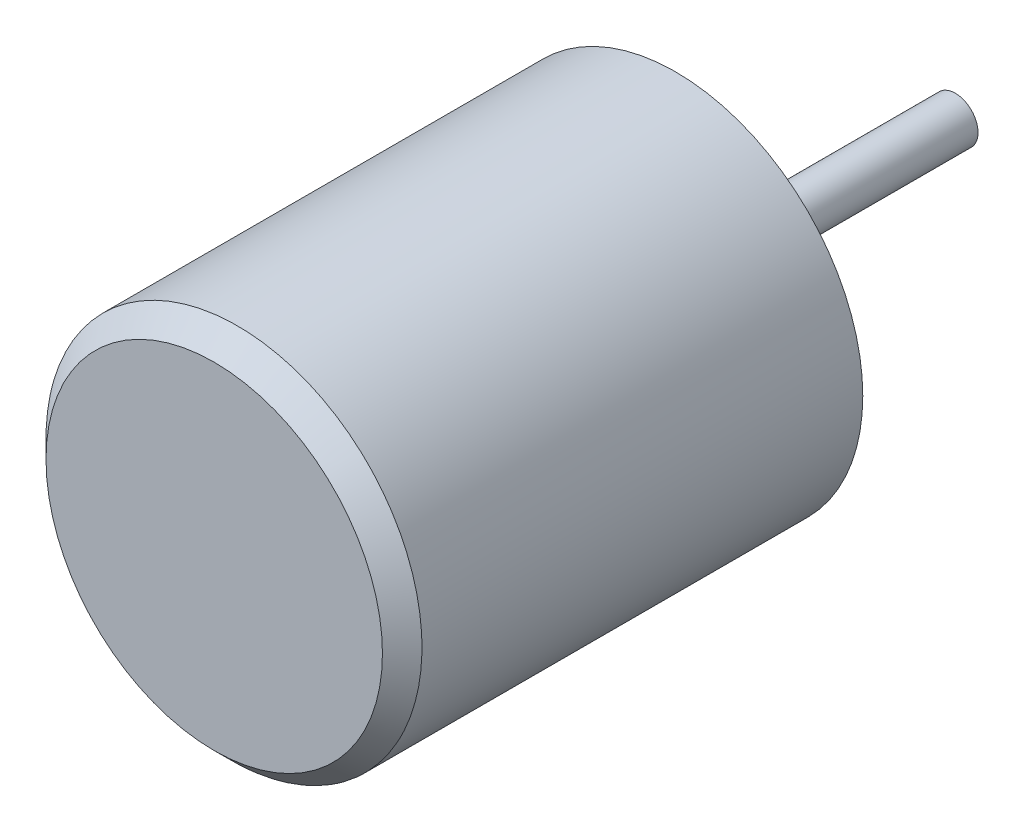
SolidWorks part; units mm, degrees
ref_plane "Front Plane" through (0, 0, 0) normal (0, 0, 1) x (1, 0, 0)
ref_plane "Top Plane" through (0, 0, 0) normal (0, 1, 0) x (1, 0, 0)
ref_plane "Right Plane" through (0, 0, 0) normal (1, 0, 0) x (0, 0, -1)
sketch "Sketch1" plane through (0, 0, 0) normal (0, 0, 1) x (1, 0, 0)
  circle A0 centre (0.5345, 0.1336) radius 13
extrude "Boss-Extrude1" add sketch "Sketch1" along normal blind 30
sketch "Sketch5" plane through (0, 0, 30) normal (0, 0, 1) x (1, 0, 0)
  circle A0 centre (0.4759, -0.0509) radius 11.687
extrude "Boss-Extrude3" add sketch "Sketch5" along normal blind 2
draft "Draft2" type of draft neutral plane draft angle 45 faces to draft 1 face at (12.1629, -0.0509, 32) neutral plane through (0.4759, -0.0509, 32) neutral plane normal (0, 0, 1) parameters "D1"=45
sketch "Sketch6" plane through (0, 0, 0) normal (0, 0, -1) x (-1, 0, 0)
  circle A0 centre (0.0355, -0.0142) radius 1.5775
extrude "Boss-Extrude4" add sketch "Sketch6" along normal blind 20
sketch "Sketch7" plane through (0, 0, -20) normal (0, 0, -1) x (-1, 0, 0)
sketch "Sketch8" plane through (0, 0, -20) normal (0, 0, -1) x (-1, 0, 0)
  circle A1 centre (0.0355, -0.0142) radius 1.5775
  circle A2 centre (0.0355, -0.0142) radius 1.5775
  dimension "D1" = 0
